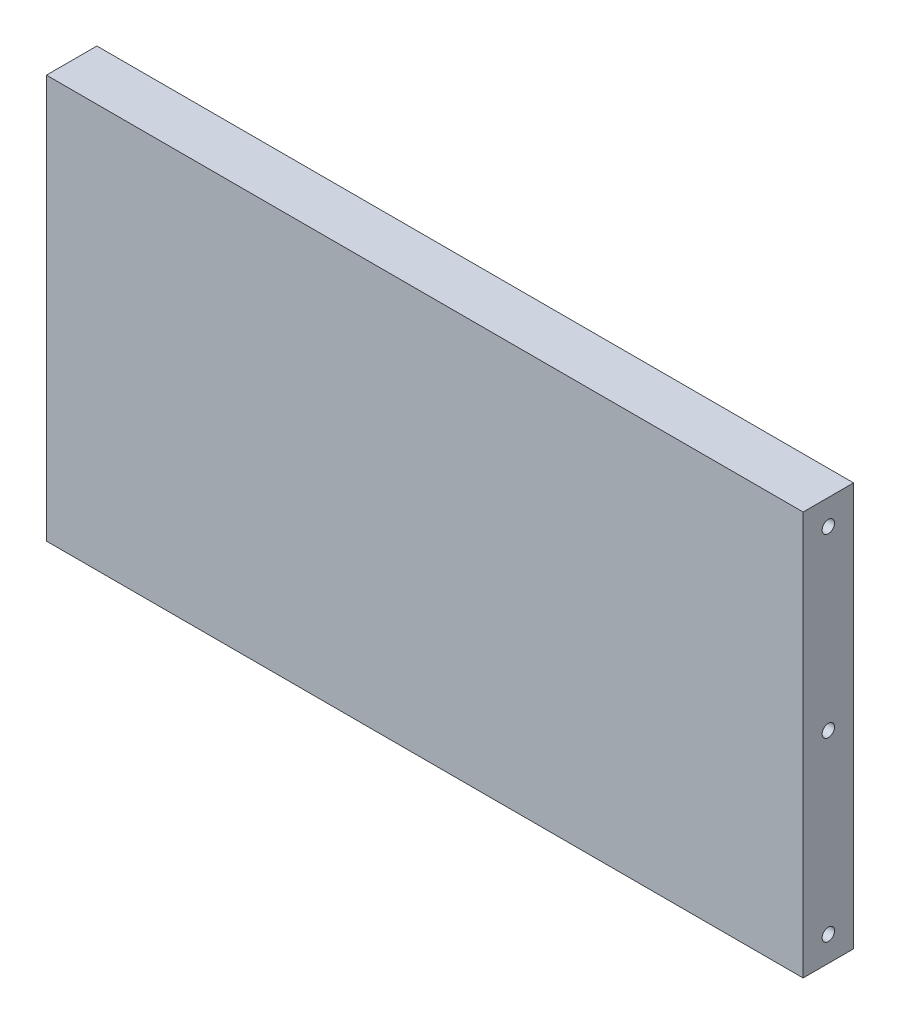
SolidWorks part; units mm, degrees
material "AISI 1020"
ref_plane "Ebene vorne" through (0, 0, 0) normal (0, 0, 1) x (1, 0, 0)
ref_plane "Ebene oben" through (0, 0, 0) normal (0, 1, 0) x (1, 0, 0)
ref_plane "Ebene rechts" through (0, 0, 0) normal (1, 0, 0) x (0, 0, -1)
sketch "Skizze1" plane through (0, 0, 0) normal (0, 0, 1) x (1, 0, 0)
  line L1 (-65.5556, 65.2273) -> (84.4444, 65.2273)
  line L2 (-65.5556, 65.2273) -> (-65.5556, -14.7727)
  line L3 (-65.5556, -14.7727) -> (84.4444, -14.7727)
  line L4 (84.4444, 65.2273) -> (84.4444, -14.7727)
  dimension "D1" = 150
  dimension "D2" = 80
extrude "Aufsatz-Linear austragen1" add sketch "Skizze1" along normal blind 10
sketch "Skizze2" plane through (-65.5556, 0, 0) normal (-1, 0, 0) x (0, 0, 1)
  line L0 (5, 60.2273) -> (5, -9.7727) construction
  line L1 (10, 65.2273) -> (0, 65.2273) construction
  line L2 (10, -14.7727) -> (0, -14.7727) construction
  line L3 (0, 65.2273) -> (0, -14.7727) construction
  circle A0 centre (5, 60.2273) radius 1.23
  circle A1 centre (5, 25.2273) radius 1.23
  circle A2 centre (5, -9.7727) radius 1.23
  dimension "D4" = 2.46
  dimension "D1" = 5
  dimension "D2" = 5
  dimension "D3" = 5
extrude "Schnitt-Linear austragen1" cut sketch "Skizze2" against normal blind 5
sketch "Skizze3" plane through (84.4444, 0, 0) normal (1, 0, 0) x (0, 0, -1)
  line L0 (-5, 60.2273) -> (-5, -9.7727) construction
  line L1 (-10, -14.7727) -> (-10, 65.2273) construction
  line L2 (-10, 65.2273) -> (0, 65.2273) construction
  line L3 (-10, -14.7727) -> (0, -14.7727) construction
  circle A0 centre (-5, 60.2273) radius 1.23
  circle A1 centre (-5, 25.2273) radius 1.23
  circle A2 centre (-5, -9.7727) radius 1.23
  dimension "D1" = 2.46
  dimension "D2" = 5
  dimension "D3" = 5
  dimension "D4" = 5
extrude "Schnitt-Linear austragen2" cut sketch "Skizze3" against normal blind 5
